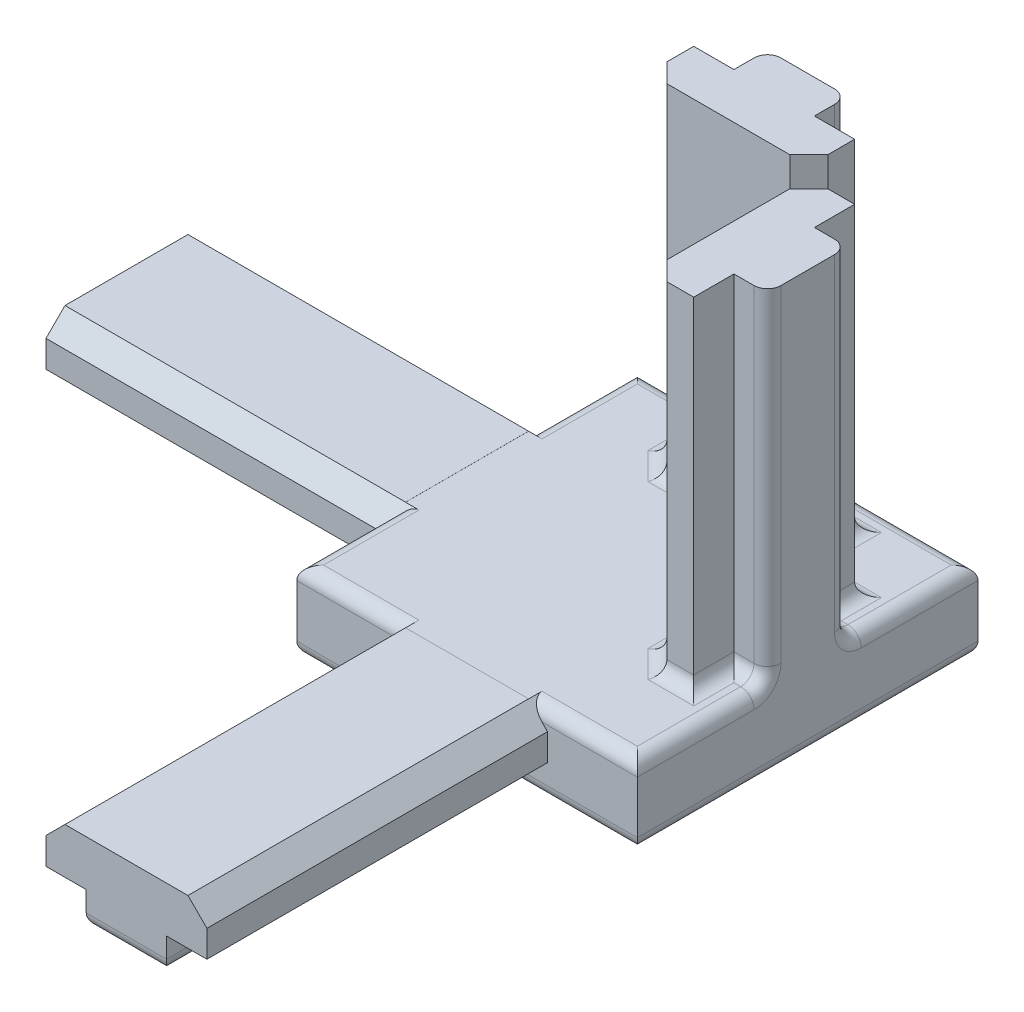
SolidWorks part; units mm, degrees
ref_plane "Front Plane" through (0, 0, 0) normal (0, 0, 1) x (1, 0, 0)
ref_plane "Top Plane" through (0, 0, 0) normal (0, 1, 0) x (1, 0, 0)
ref_plane "Right Plane" through (0, 0, 0) normal (1, 0, 0) x (0, 0, -1)
sketch "Sketch1" plane through (0, 0, 0) normal (0, 1, 0) x (1, 0, 0)
  line L1 (-12.7, 12.7) -> (12.7, 12.7)
  line L2 (-12.7, 12.7) -> (-12.7, -12.7)
  line L3 (-12.7, -12.7) -> (12.7, -12.7)
  line L4 (12.7, 12.7) -> (12.7, -12.7)
  line L5 (-12.7, 12.7) -> (12.7, -12.7) construction
  line L6 (-12.7, -12.7) -> (12.7, 12.7) construction
  point P0 (0, 0)
  dimension "D1" = 25.4
extrude "Boss-Extrude1" add sketch "Sketch1" along normal blind 5.91
sketch "Sketch2" plane through (0, 0, 12.7) normal (0, 0, 1) x (1, 0, 0)
  line L0 (-3, 0) -> (3, 0)
  line L1 (-12.7, 0) -> (12.7, 0) construction
  line L2 (3, 0) -> (3, 2.5)
  line L3 (3, 2.5) -> (6, 2.5)
  line L4 (6, 2.5) -> (6, 4.5)
  line L5 (6, 4.5) -> (4.5858, 5.9142)
  line L6 (4.5858, 5.9142) -> (-4.5858, 5.9142)
  line L7 (0, 0) -> (0, 6.6193) construction
  line L8 (-6, 4.5) -> (-4.5858, 5.9142)
  line L9 (-6, 2.5) -> (-6, 4.5)
  line L10 (-3, 2.5) -> (-6, 2.5)
  line L11 (-3, 0) -> (-3, 2.5)
  point P12 (4.8072, 5.2674)
  point P14 (0, 5.9142)
  point P18 (0, 0)
  dimension "D1" = 6
  dimension "D2" = 12
  dimension "D3" = 135
  dimension "D4" = 2.5
  dimension "D5" = 2
extrude "Boss-Extrude2" add sketch "Sketch2" along normal blind 25.4
sketch "Sketch3" plane through (-12.7, 0, 0) normal (-1, 0, 0) x (0, 0, 1)
  line L0 (-3, 0) -> (3, 0)
  line L1 (3, 0) -> (3, 2.5)
  line L2 (3, 2.5) -> (6, 2.5)
  line L3 (6, 2.5) -> (6, 4.5)
  line L4 (6, 4.5) -> (4.5858, 5.9142)
  line L5 (4.5858, 5.9142) -> (-4.5858, 5.9142)
  line L6 (0, 0) -> (0, 6.6193) construction
  line L7 (-6, 4.5) -> (-4.5858, 5.9142)
  line L8 (-6, 2.5) -> (-6, 4.5)
  line L9 (-3, 2.5) -> (-6, 2.5)
  line L10 (-3, 0) -> (-3, 2.5)
  point P9 (0, 5.9142)
  point P13 (0, 0)
  dimension "D1" = 6
  dimension "D2" = 12
  dimension "D3" = 2.5
  dimension "D4" = 2
  dimension "D5" = 135
extrude "Boss-Extrude3" add sketch "Sketch3" along normal blind 25.4
sketch "Sketch5" plane through (0, 5.91, 0) normal (0, 1, 0) x (1, 0, 0)
  line L0 (3, 12.7) -> (-3, 12.7)
  line L1 (-3, 12.7) -> (-3, 10.2)
  line L2 (-3, 10.2) -> (-6, 10.2)
  line L3 (-6, 10.2) -> (-6, 8.2)
  line L4 (-6, 8.2) -> (-4.5858, 6.7858)
  line L5 (-4.5858, 6.7858) -> (4.5858, 6.7858)
  line L6 (0, 3.4686) -> (0, -3.1261) construction
  line L7 (6, 8.2) -> (4.5858, 6.7858)
  line L8 (6, 10.2) -> (6, 8.2)
  line L9 (3, 10.2) -> (6, 10.2)
  line L10 (3, 12.7) -> (3, 10.2)
  line L11 (12.7, 12.7) -> (-12.7, 12.7) construction
  line L12 (12.7, -3) -> (12.7, 3)
  line L13 (12.7, 3) -> (10.2, 3)
  line L14 (10.2, 3) -> (10.2, 6)
  line L15 (10.2, 6) -> (8.2, 6)
  line L16 (8.2, 6) -> (6.7858, 4.5858)
  line L17 (6.7858, 4.5858) -> (6.7858, -4.5858)
  line L18 (6.7858, 0) -> (12.7, 0) construction
  line L19 (8.2, -6) -> (6.7858, -4.5858)
  line L20 (10.2, -6) -> (8.2, -6)
  line L21 (10.2, -3) -> (10.2, -6)
  line L22 (12.7, -3) -> (10.2, -3)
  line L23 (12.7, -12.7) -> (12.7, 12.7) construction
  point P9 (0, 6.7858)
  point P13 (0, 12.7)
  point P27 (6.7858, 0)
  point P31 (12.7, 0)
  point P33 (0, 0)
  point P34 (0, 0)
  dimension "D1" = 6
  dimension "D2" = 12
  dimension "D3" = 2.5
  dimension "D4" = 2
  dimension "D5" = 135
  dimension "D6" = 2.5
  dimension "D7" = 6
  dimension "D8" = 12
  dimension "D9" = 2
  dimension "D10" = 135
  dimension "D11" = 135
extrude "Boss-Extrude4" add sketch "Sketch5" along normal blind 25.4
fillet "Fillet2" radius 1 42 edges at (3, 18.61, -12.7) (12.7, 18.61, -3) (12.7, 18.61, 3) (-3, 18.61, -12.7) (-6, 5.91, -9.2) (-5.2929, 5.91, -7.4929) (0, 5.91, -6.7858) (5.2929, 5.91, -7.4929) (6, 5.91, -9.2) (4.5, 5.91, -10.2) (3, 5.91, -11.45) (7.85, 5.91, -12.7) (12.7, 5.91, -7.85) (11.45, 5.91, -3) (10.2, 5.91, -4.5) (9.2, 5.91, -6) (7.4929, 5.91, -5.2929) (6.7858, 5.91, 0) (7.4929, 5.91, 5.2929) (9.2, 5.91, 6) (10.2, 5.91, 4.5) (11.45, 5.91, 3) (12.7, 5.91, 7.85) (8.645, 5.91, 12.7) (-8.645, 5.91, 12.7) (-12.7, 5.91, 8.645) (-12.7, 5.91, -8.645) (-7.85, 5.91, -12.7) (-3, 5.91, -11.45) (-4.5, 5.91, -10.2) (0, 0, -12.7) (-12.7, 0, -7.85) (-25.4, 0, -3) (-38.1, 0, 0) (-25.4, 0, 3) (-12.7, 0, 7.85) (-7.85, 0, 12.7) (-3, 0, 25.4) (0, 0, 38.1) (3, 0, 25.4) (7.85, 0, 12.7) (12.7, 0, 0)
equation "\"Insert Lengths\"= 1in"
equation "\"D1@Boss-Extrude2\"=\"Insert Lengths\""
equation "\"D1@Boss-Extrude4\"=\"Insert Lengths\""
